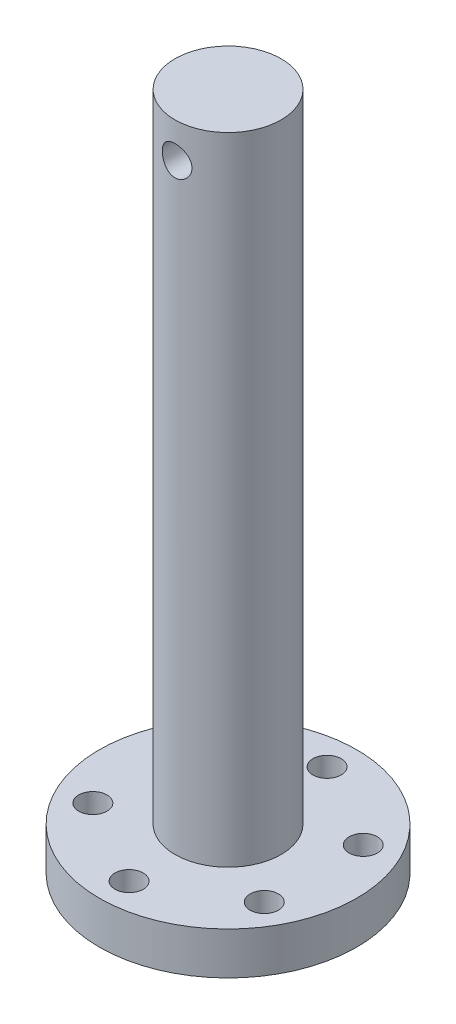
SolidWorks part; units mm, degrees
other "Markup1"
sketch "Sketch8" plane through (-18.2, 139.0587, 44.2712) normal (-0.535, 0.1154, 0.8369) x (0.8383, -0.0507, 0.5428)
other "Markup2"
sketch "Sketch10" plane through (-18.2, 96, -18.2) normal (-0.228, 0.8172, -0.5293) x (-0.8762, 0.0648, 0.4775)
ref_plane "Front Plane" through (0, 0, 0) normal (0, 0, 1) x (1, 0, 0)
ref_plane "Top Plane" through (0, 0, 0) normal (0, 1, 0) x (1, 0, 0)
ref_plane "Right Plane" through (0, 0, 0) normal (1, 0, 0) x (0, 0, -1)
sketch "Sketch1" plane through (0, 0, 0) normal (0, 1, 0) x (1, 0, 0)
  circle A0 centre (0, 0) radius 18.2
  dimension "D1" = 36.4
extrude "Boss-Extrude1" add sketch "Sketch1" along normal blind 6
sketch "Sketch3" plane through (0, 6, 0) normal (0, 1, 0) x (1, 0, 0)
  circle A0 centre (0, 14) radius 2
  dimension "D1" = 4
  dimension "D2" = 14
extrude "Cut-Extrude1" cut sketch "Sketch3" against normal blind 10
pattern_circular "CirPattern1" count 6 over 360 about axis through (0, 6, 0) along (0, 1, 0) of "Cut-Extrude1"
sketch "Sketch4" plane through (0, 6, 0) normal (0, 1, 0) x (1, 0, 0)
  circle A0 centre (0, 0) radius 7.5
  dimension "D1" = 15
extrude "Boss-Extrude2" add sketch "Sketch4" along normal blind 90
sketch "Sketch7" plane through (0, 0, 0) normal (1, 0, 0) x (0, 0, -1)
  line L0 (7.5, 96) -> (-7.5, 96) construction
  spline S0 degree 2 poles (0, 96) (-1.7427, 134.9143) (-44.0761, 130.8588) knots 0 0 0 1 1 1
ref_plane "Plane1" through (0, 0, -7.5) normal (0, 0, -1) x (-1, 0, 0)
sketch "Sketch9" plane through (0, 0, -7.5) normal (0, 0, -1) x (-1, 0, 0)
  line L0 (7.5, 96) -> (-7.5, 96) construction
  circle A0 centre (0, 91) radius 2.1
  dimension "D1" = 5
extrude "Cut-Extrude2" cut sketch "Sketch9" against normal through all
